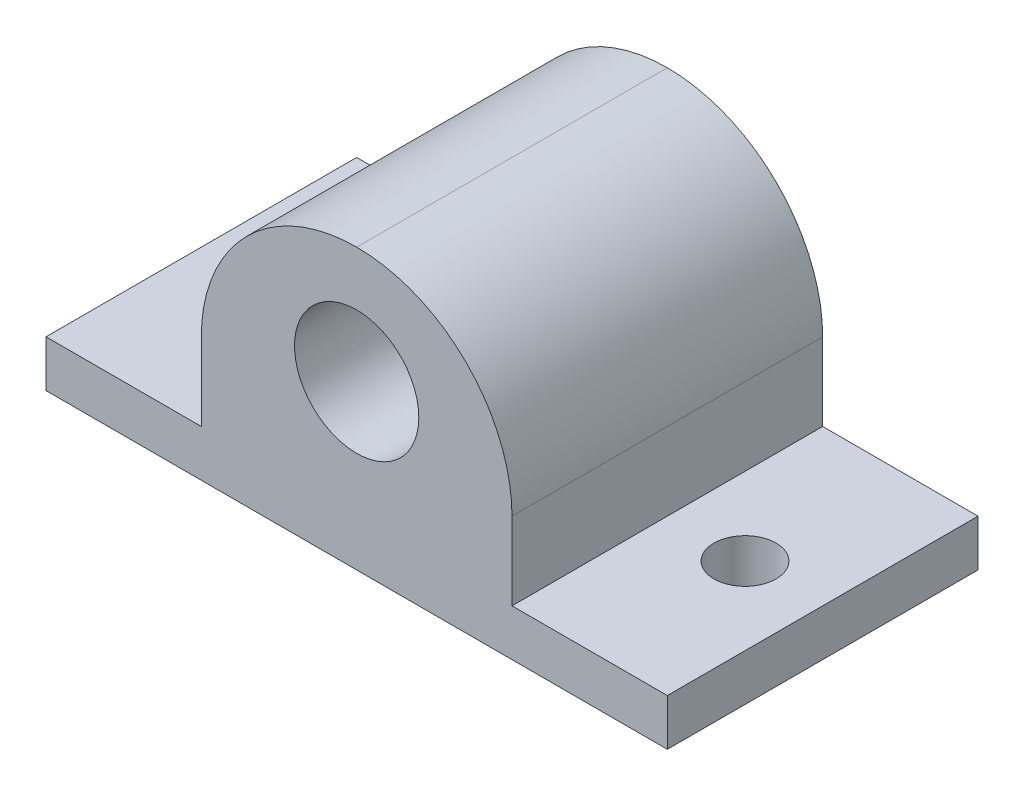
SolidWorks part; units mm, degrees
ref_plane "Front Plane" through (0, 0, 0) normal (0, 0, 1) x (1, 0, 0)
ref_plane "Top Plane" through (0, 0, 0) normal (0, 1, 0) x (1, 0, 0)
ref_plane "Right Plane" through (0, 0, 0) normal (1, 0, 0) x (0, 0, -1)
sketch "Sketch1" plane through (0, 0, 0) normal (0, 1, 0) x (1, 0, 0)
  line L1 (0, 0) -> (40, 0)
  line L2 (0, 0) -> (0, 20)
  line L3 (0, 20) -> (40, 20)
  line L4 (40, 0) -> (40, 20)
  dimension "D1" = 20
  dimension "D2" = 40
extrude "Boss-Extrude1" add sketch "Sketch1" along normal blind 3
sketch "Sketch2" plane through (0, 3, 0) normal (0, 1, 0) x (1, 0, 0)
  line L0 (40, 20) -> (0, 20) construction
  line L1 (10, 20) -> (30, 20)
  line L2 (10, 20) -> (10, 0)
  line L3 (10, 0) -> (30, 0)
  line L4 (30, 20) -> (30, 0)
  line L5 (0, 0) -> (40, 0) construction
  line L6 (0, 20) -> (0, 0) construction
  line L7 (40, 0) -> (40, 20) construction
  dimension "D1" = 10
  dimension "D2" = 10
extrude "Boss-Extrude2" add sketch "Sketch2" along normal blind 15
sketch "Sketch3" plane through (0, 0, 0) normal (0, 0, 1) x (1, 0, 0)
  line L0 (10, 18) -> (10, 3) construction
  line L2 (10, 18) -> (30, 18) construction
  circle A0 centre (20, 10.5) radius 4
  dimension "D2" = 8
  dimension "D1" = 10
  dimension "D3" = 7.5
extrude "Cut-Extrude1" cut sketch "Sketch3" against normal through all
fillet "Fillet1" radius 10 2 edges at (30, 18, -10) (10, 18, -10)
sketch "Sketch4" plane through (0, 3, 0) normal (0, 1, 0) x (1, 0, 0)
  line L0 (40, 0) -> (40, 20) construction
  line L1 (40, 20) -> (30, 20) construction
  line L2 (0, 20) -> (0, 0) construction
  line L3 (10, 20) -> (0, 20) construction
  circle A0 centre (35, 10) radius 2
  circle A1 centre (5, 10) radius 2
  dimension "D1" = 4
  dimension "D6" = 4
  dimension "D2" = 5
  dimension "D3" = 10
  dimension "D4" = 5
  dimension "D5" = 10
extrude "Cut-Extrude2" cut sketch "Sketch4" against normal through all
